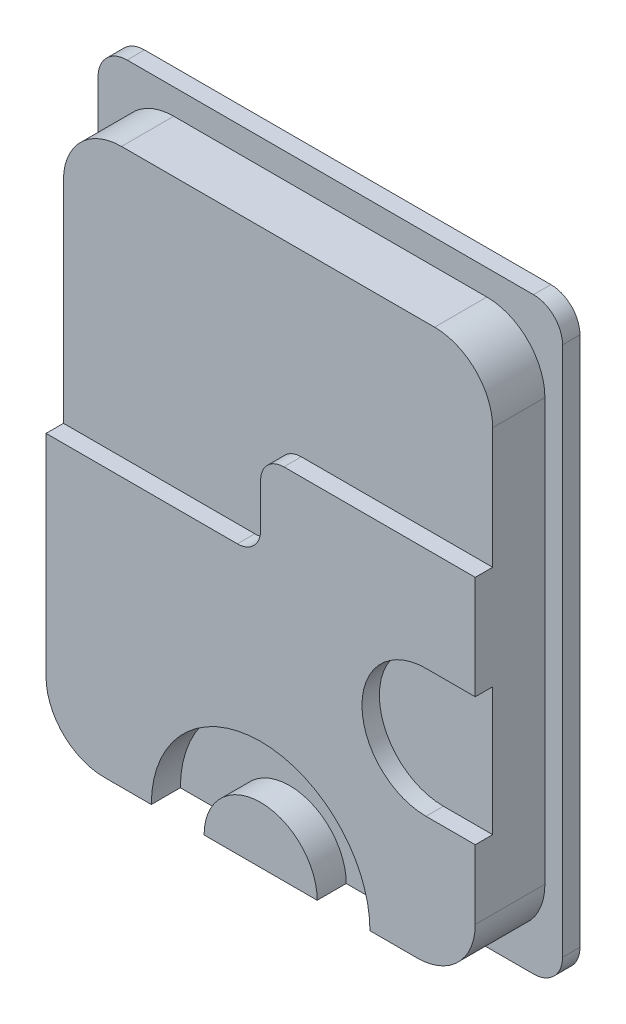
SolidWorks part; units mm, degrees
material "6061 Alloy"
ref_plane "Front Plane" through (0, 0, 0) normal (0, 0, 1) x (1, 0, 0)
ref_plane "Top Plane" through (0, 0, 0) normal (0, 1, 0) x (1, 0, 0)
ref_plane "Right Plane" through (0, 0, 0) normal (1, 0, 0) x (0, 0, -1)
sketch "Sketch1" plane through (0, 0, 0) normal (0, 0, 1) x (1, 0, 0)
  line L13 (5, 0) -> (75, 0)
  line L14 (0, 5) -> (0, 96.346)
  line L15 (5, 101.346) -> (75, 101.346)
  line L16 (80, 5) -> (80, 96.346)
  arc A0 (5, 0) -> (0, 5) centre (5, 5) cw
  arc A1 (75, 0) -> (80, 5) centre (75, 5) ccw
  arc A2 (75, 101.346) -> (80, 96.346) centre (75, 96.346) cw
  arc A3 (0, 96.346) -> (5, 101.346) centre (5, 96.346) cw
  point P5 (0, 0)
  point P7 (0, 0)
  point P9 (0, 0)
  dimension "D1" = 5
extrude "Boss-Extrude1" add sketch "Sketch1" along normal blind 15
ref_point "Point1"
sketch "Sketch3" plane through (0, 0, 15) normal (0, 0, 1) x (1, 0, 0)
  line L1 (13.037, 4.3718) -> (66.963, 4.3718)
  line L2 (3.037, 14.3718) -> (3.037, 86.9742)
  line L3 (13.037, 96.9742) -> (66.963, 96.9742)
  line L4 (76.963, 14.3718) -> (76.963, 86.9742)
  line L5 (3.037, 4.3718) -> (76.963, 96.9742) construction
  line L6 (3.037, 96.9742) -> (76.963, 4.3718) construction
  line L7 (-12.212, -10.0064) -> (92.212, -10.0064)
  line L8 (-12.212, -10.0064) -> (-12.212, 111.3524)
  line L9 (-12.212, 111.3524) -> (92.212, 111.3524)
  line L10 (92.212, -10.0064) -> (92.212, 111.3524)
  line L11 (-12.212, -10.0064) -> (92.212, 111.3524) construction
  line L12 (-12.212, 111.3524) -> (92.212, -10.0064) construction
  arc A0 (13.037, 4.3718) -> (3.037, 14.3718) centre (13.037, 14.3718) cw
  arc A1 (66.963, 4.3718) -> (76.963, 14.3718) centre (66.963, 14.3718) ccw
  arc A2 (66.963, 96.9742) -> (76.963, 86.9742) centre (66.963, 86.9742) cw
  arc A3 (3.037, 86.9742) -> (13.037, 96.9742) centre (13.037, 86.9742) cw
  point P0 (40, 50.673)
  point P6 (40, 50.673)
  dimension "D1" = 10
extrude "Cut-Extrude1" cut sketch "Sketch3" against normal blind 12
sketch "Sketch4" plane through (0, 0, 15) normal (0, 0, 1) x (1, 0, 0)
  line L0 (36, 50.673) -> (3.037, 50.673)
  line L1 (3.037, 86.9742) -> (3.037, 14.3718) construction
  line L2 (40, 54.673) -> (40, 62.1591)
  line L3 (44, 66.1591) -> (76.963, 66.1591)
  line L4 (76.963, 14.3718) -> (76.963, 86.9742) construction
  line L5 (3.037, 50.673) -> (3.037, 113.1352)
  line L6 (3.037, 113.1352) -> (76.963, 113.1352)
  line L7 (76.963, 113.1352) -> (76.963, 66.1591)
  arc A0 (40, 62.1591) -> (44, 66.1591) centre (44, 62.1591) cw
  arc A1 (36, 50.673) -> (40, 54.673) centre (36, 54.673) ccw
  point P13 (40, 50.673)
  dimension "D1" = 4
  dimension "D2" = 4
extrude "Cut-Extrude2" cut sketch "Sketch4" against normal blind 3
sketch "Sketch5" plane through (0, 0, 15) normal (0, 0, 1) x (1, 0, 0)
  line L0 (83.7106, 37.3053) -> (68.4819, 37.3053) construction
  line L1 (83.7106, 26.2747) -> (68.4819, 26.2747)
  line L2 (83.7106, 48.3359) -> (68.4819, 48.3359)
  arc A0 (83.7106, 26.2747) -> (83.7106, 48.3359) centre (83.7106, 37.3053) ccw
  arc A1 (68.4819, 48.3359) -> (68.4819, 26.2747) centre (68.4819, 37.3053) ccw
  point P2 (76.0963, 37.3053)
extrude "Cut-Extrude3" cut sketch "Sketch5" against normal blind 3
sketch "Sketch6" plane through (0, 0, 15) normal (0, 0, 1) x (1, 0, 0)
  line L0 (13.037, 4.3718) -> (66.963, 4.3718) construction
  circle A0 centre (40, 4.3718) radius 18.8281
  circle A1 centre (40, 4.3718) radius 9.7394
extrude "Cut-Extrude4" cut sketch "Sketch6" against normal blind 5
